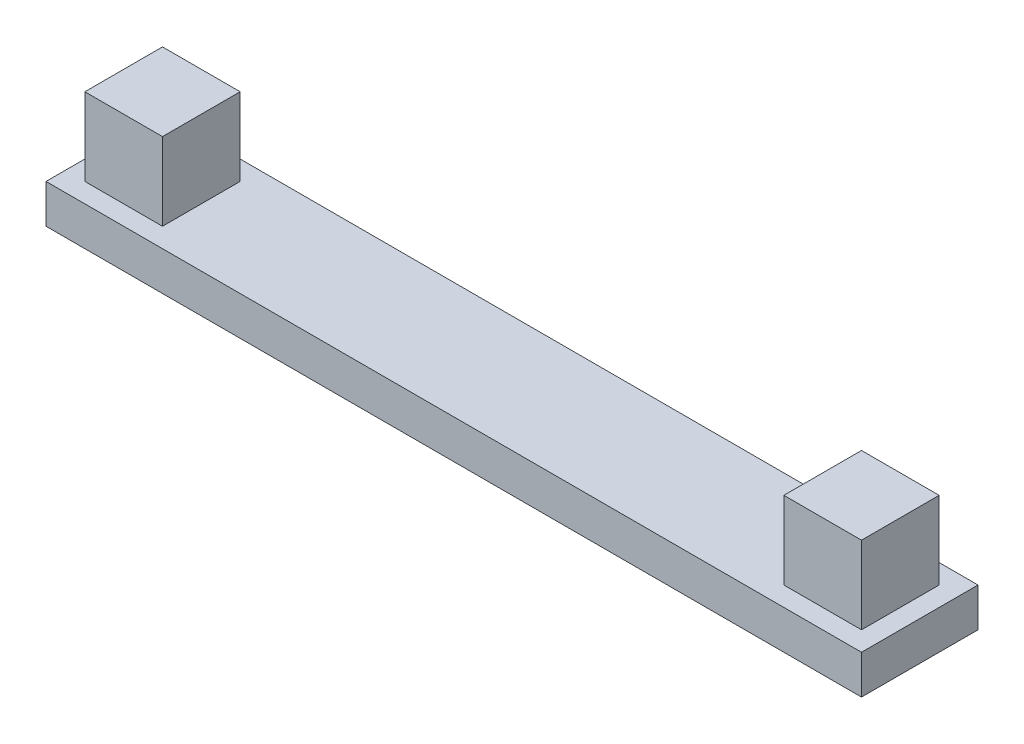
SolidWorks part; units mm, degrees
ref_plane "Front Plane" through (0, 0, 0) normal (0, 0, 1) x (1, 0, 0)
ref_plane "Top Plane" through (0, 0, 0) normal (0, 1, 0) x (1, 0, 0)
ref_plane "Right Plane" through (0, 0, 0) normal (1, 0, 0) x (0, 0, -1)
sketch "Sketch1" plane through (0, 0, 0) normal (0, 1, 0) x (1, 0, 0)
  line L1 (0, 0) -> (21, 0)
  line L2 (0, 0) -> (0, 3)
  line L3 (0, 3) -> (21, 3)
  line L4 (21, 0) -> (21, 3)
  line L5 (0, 0) -> (21, 3) construction
  line L6 (0, 3) -> (21, 0) construction
  line L7 (0.5, 2.5) -> (2.5, 2.5)
  line L8 (0.5, 2.5) -> (0.5, 0.5)
  line L9 (0.5, 0.5) -> (2.5, 0.5)
  line L10 (2.5, 2.5) -> (2.5, 0.5)
  line L11 (0.5, 2.5) -> (2.5, 0.5) construction
  line L12 (0.5, 0.5) -> (2.5, 2.5) construction
  line L13 (18.5, 2.5) -> (20.5, 2.5)
  line L14 (18.5, 2.5) -> (18.5, 0.5)
  line L15 (18.5, 0.5) -> (20.5, 0.5)
  line L16 (20.5, 2.5) -> (20.5, 0.5)
  line L17 (18.5, 2.5) -> (20.5, 0.5) construction
  line L18 (18.5, 0.5) -> (20.5, 2.5) construction
  point P4 (10.5, 1.5)
  point P10 (1.5, 1.5)
  point P15 (19.5, 1.5)
  point P17 (0, 1.5)
  point P22 (21, 1.5)
  dimension "D1" = 21
  dimension "D2" = 3
  dimension "D3" = 18
  dimension "D4" = 2
  dimension "D5" = 9
extrude "Boss-Extrude1" add sketch "Sketch1" along normal blind 1 contours L1 L4 L3 L2 L7 L10 L9 L8 L13 L16 L15 L14 region at (10.5, 0, -1.5)
ref_plane "Plane1" through (2.5, 0, -2.5) normal (1, 0, 0) x (0, 0, -1)
extrude "Boss-Extrude2" add sketch "Sketch1<3>" along normal blind 3 contours L7 L10 L9 L8 | L13 L16 L15 L14
sketch "Sketch1<3>" plane through (0, 0, 0) normal (0, 1, 0) x (1, 0, 0) same geometry as "Sketch1"
